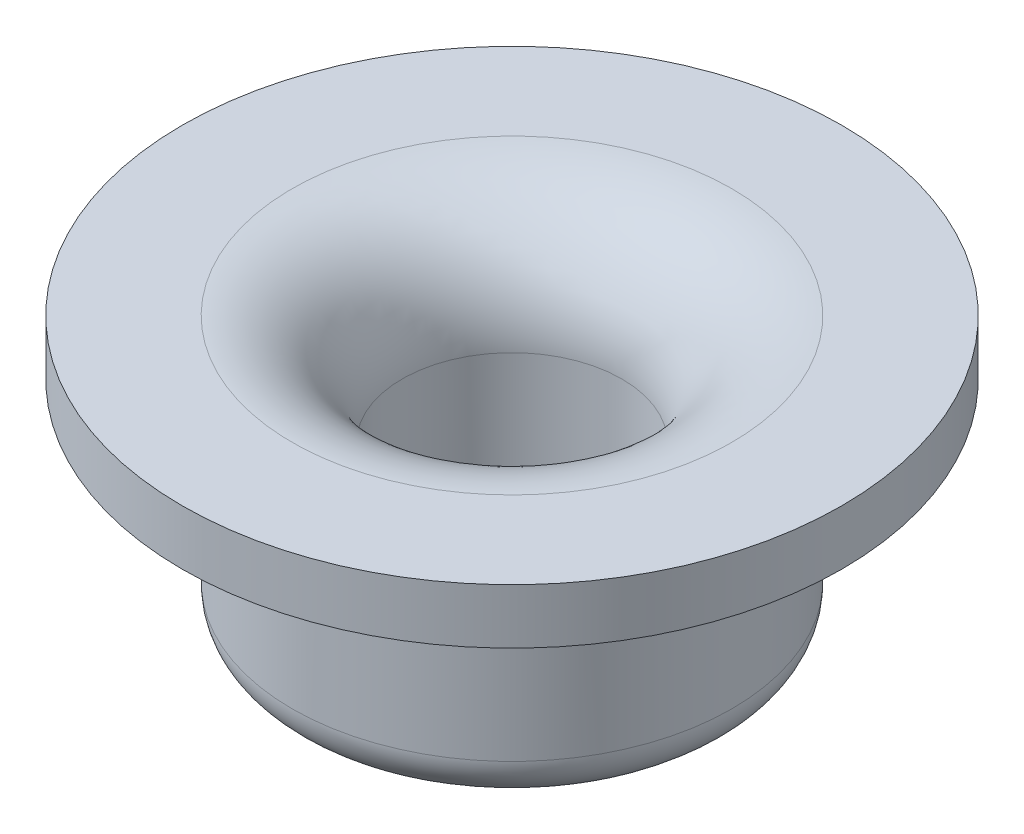
SolidWorks part; units mm, degrees
ref_plane "Front Plane" through (0, 0, 0) normal (0, 0, 1) x (1, 0, 0)
ref_plane "Top Plane" through (0, 0, 0) normal (0, 1, 0) x (1, 0, 0)
ref_plane "Right Plane" through (0, 0, 0) normal (1, 0, 0) x (0, 0, -1)
sketch "Sketch1" plane through (0, 0, 0) normal (1, 0, 0) x (0, 0, -1)
  line L0 (-3.175, 0) -> (-3.175, 7.9375)
  line L1 (-3.175, 7.9375) -> (-9.525, 7.9375)
  line L2 (-9.525, 7.9375) -> (-9.525, 6.35)
  line L3 (-9.525, 6.35) -> (-6.35, 6.35)
  line L4 (-6.35, 6.35) -> (-6.35, 0)
  line L5 (-6.35, 0) -> (-3.175, 0)
  point P6 (-7.3607, 5.9333)
  point P7 (0, 0)
  dimension "D1" = 3.175
  dimension "D2" = 6.35
  dimension "D3" = 7.9375
  dimension "D4" = 6.35
  dimension "D5" = 9.525
ref_axis "Axis1" through (0, 0, 0) along (0, 1, 0)
revolve "Revolve1" add sketch "Sketch1" angle 360 about axis through (0, 0, 0) along (0, 1, 0)
fillet "Fillet1" radius 3.175 1 edges at (0, 7.9375, -3.175)
fillet "Fillet4" radius 1.27 2 edges at (0, 0, -6.35) (0, 0, -3.175)
